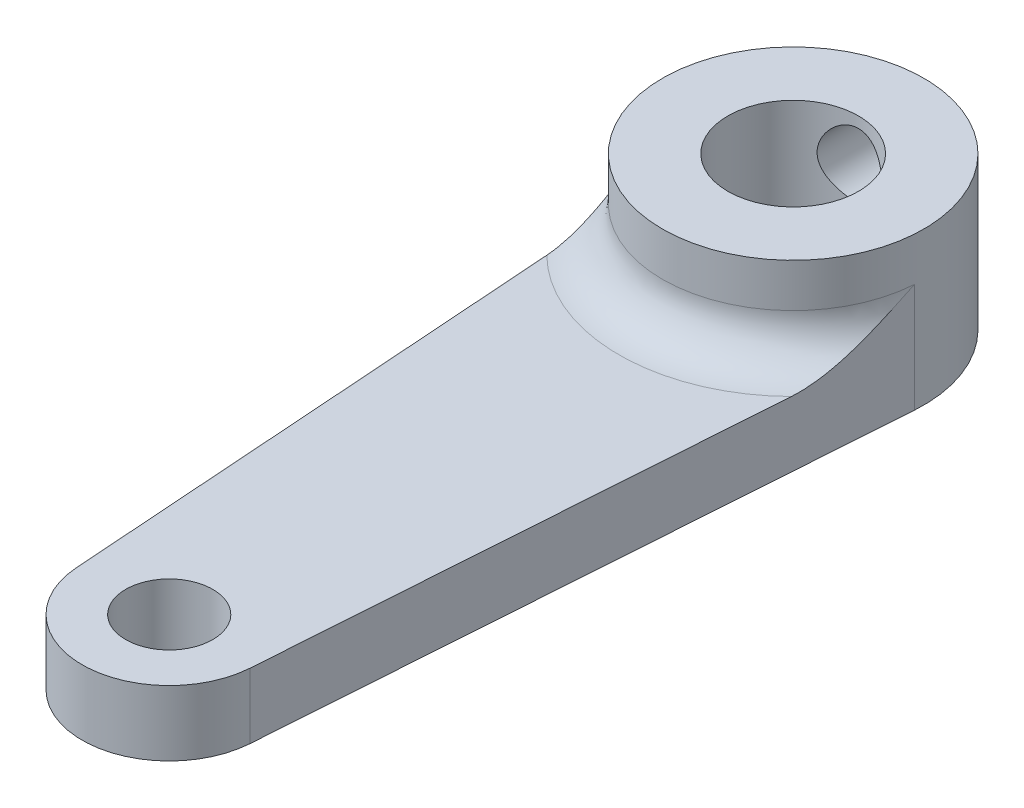
SolidWorks part; units mm, degrees
ref_plane "Front Plane" through (0, 0, 0) normal (0, 0, 1) x (1, 0, 0)
ref_plane "Top Plane" through (0, 0, 0) normal (0, 1, 0) x (1, 0, 0)
ref_plane "Right Plane" through (0, 0, 0) normal (1, 0, 0) x (0, 0, -1)
sketch "Sketch1" plane through (0, 0, 0) normal (0, 1, 0) x (1, 0, 0)
  line L0 (0, 0) -> (0, -28.6456) construction
  line L1 (-5.9854, -0.4189) -> (-3.9902, -28.9249)
  line L2 (5.9854, -0.4189) -> (3.9902, -28.9249)
  circle A0 centre (0, 0) radius 6
  circle A1 centre (0, -28.6456) radius 4
  circle A2 centre (0, -28.6456) radius 2
  circle A3 centre (0, 0) radius 3
  dimension "D1" = 12
  dimension "D2" = 8
  dimension "D3" = 4
  dimension "D4" = 6
extrude "Boss-Extrude1" add sketch "Sketch1" along normal mid plane 3 contours A0 L0 A1 L2 | L0 A0 L1 A1 | A1 A2 | A3 A0 region at (-3.9761, 0, 4.2641) region at (2.6405, 0, 14.6855) region at (-2.6405, 0, 14.6855) region at (2.7484, 0, 25.8972)
sketch "Sketch2" plane through (0, 1.5, 0) normal (0, 1, 0) x (1, 0, 0)
  circle A0 centre (0, 0) radius 3
  circle A1 centre (0, 0) radius 6
extrude "Boss-Extrude2" add sketch "Sketch2" along normal blind 4
fillet "Fillet1" radius 2 1 edges at (0, 1.5, 6)
sketch "Sketch3" plane through (0, -1.5, 0) normal (0, -1, 0) x (1, 0, 0)
  line L0 (-7.6506, -7) -> (8.3494, -7)
  dimension "D1" = 7
  dimension "D2" = 16
extrude "Extrude-Thin1" add sketch "Sketch3" against normal blind 10 separate body thin thin type one direction wall 1
hole_wizard "M3 Tapped Hole1" positions "Sketch4" profile "Sketch5" tap size "M3" standard "ISO"
sketch "Sketch4" plane through (0, 0, -8) normal (0, 0, -1) x (-1, 0, 0)
  point P0 (0, 3.5)
  dimension "D1" = 3.5
sketch "Sketch5" plane through (0, 3.5, -8) normal (1, 0, 0) x (0, 1, 0)
  line L0 (0, 0) -> (0, 10.4013)
  line L1 (0, 10.4013) -> (1.5, 9.5)
  line L2 (1.5, 9.5) -> (1.5, 0.025)
  line L3 (1.5, 0.025) -> (1.525, 0)
  line L5 (1.525, 0) -> (0, 0)
  line L6 (-1.5, 0.025) -> (-1.525, 0) construction
  line L10 (0, 10.4013) -> (-1.5, 9.5) construction
  line L11 (0, -6.35) -> (0, 107.95) construction
  dimension "Tap Drill Dia." = 3
  dimension "Tap Drill Depth" = 9.5
  dimension "Near C'Sink Dia." = 3.05
  dimension "Near C'Sink Angle" = 90
  dimension "Drill Angle" = 118
cosmetic thread "Hole Thread1" parameters "D1"=5.4019, "D2"=3
sketch "Sketch6" plane through (0, 8.5, 0) normal (0, 1, 0) x (1, 0, 0)
  line L1 (8.3494, 8) -> (-7.6506, 8)
  line L2 (8.3494, 8) -> (8.3494, 7)
  line L3 (8.3494, 7) -> (-7.6506, 7)
  line L4 (-7.6506, 8) -> (-7.6506, 7)
extrude "Cut-Extrude1" cut sketch "Sketch6" against normal through all
